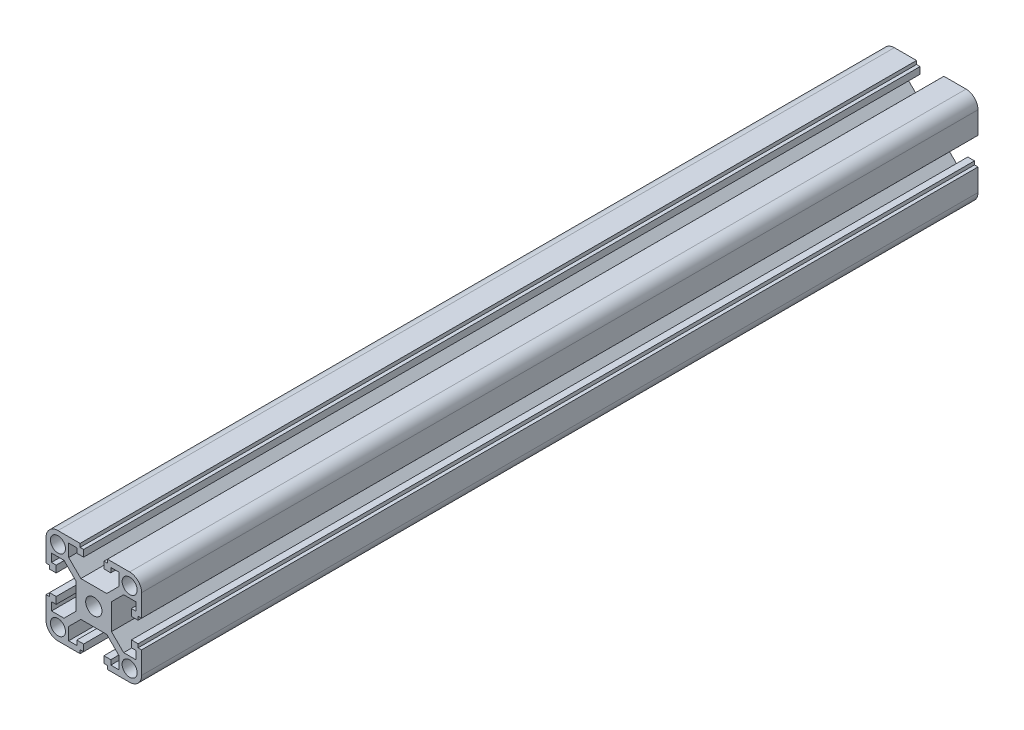
SolidWorks part; units mm, degrees
material "АД1 ГОСТ 4784-97"
ref_plane "Спереди" through (0, 0, 0) normal (0, 0, 1) x (1, 0, 0)
ref_plane "Сверху" through (0, 0, 0) normal (0, 1, 0) x (1, 0, 0)
ref_plane "Справа" through (0, 0, 0) normal (1, 0, 0) x (0, 0, -1)
ref_axis "ОсьX" through (-88.99, 0, 0) along (1, 0, 0)
ref_axis "ОсьZ" through (0, 55, 0) along (0, -1, 0)
ref_axis "ОсьY" through (0, 0, -88.99) along (0, 0, 1)
sketch "Эскиз1" plane through (0, 0, 0) normal (0, 0, 1) x (1, 0, 0)
  line L0 (-15, 20) -> (-5.7274, 20)
  line L1 (-5.7274, 20) -> (-5.7274, 18.5304)
  line L2 (-5.7274, 18.5304) -> (-4.25, 18.5304)
  line L3 (-4.25, 18.5304) -> (-4.25, 15.732)
  line L4 (-4.25, 15.732) -> (-7.1118, 15.732)
  line L5 (-7.1118, 15.732) -> (-7.1118, 17.7)
  line L6 (-7.1118, 17.7) -> (-10.5, 17.7)
  line L7 (-10.5, 17.7) -> (-10.5, 12.4799)
  line L8 (-10.5, 12.4799) -> (-5.4201, 7.4)
  line L9 (-20, 15) -> (-20, 5.7274)
  line L10 (0, 0) -> (0, 8.4096) construction
  line L11 (-15, 15) -> (0, 0) construction
  line L12 (10.5, 12.4799) -> (5.4201, 7.4)
  line L13 (10.5, 17.7) -> (10.5, 12.4799)
  line L14 (7.1118, 17.7) -> (10.5, 17.7)
  line L15 (7.1118, 15.732) -> (7.1118, 17.7)
  line L16 (4.25, 15.732) -> (7.1118, 15.732)
  line L17 (4.25, 18.5304) -> (4.25, 15.732)
  line L18 (5.7274, 18.5304) -> (4.25, 18.5304)
  line L19 (5.7274, 20) -> (5.7274, 18.5304)
  line L20 (15, 20) -> (5.7274, 20)
  line L21 (-5.4201, 7.4) -> (5.4201, 7.4)
  line L22 (-8.8445, 0) -> (0, 0) construction
  line L23 (-12.4799, 10.5) -> (-7.4, 5.4201)
  line L24 (-17.7, 10.5) -> (-12.4799, 10.5)
  line L25 (-17.7, 7.1118) -> (-17.7, 10.5)
  line L26 (-15.732, 7.1118) -> (-17.7, 7.1118)
  line L27 (-15.732, 4.25) -> (-15.732, 7.1118)
  line L28 (-18.5304, 4.25) -> (-15.732, 4.25)
  line L29 (-18.5304, 5.7274) -> (-18.5304, 4.25)
  line L30 (-20, 5.7274) -> (-18.5304, 5.7274)
  line L31 (18.5304, 5.7274) -> (18.5304, 4.25)
  line L32 (18.5304, 4.25) -> (15.732, 4.25)
  line L33 (15.732, 4.25) -> (15.732, 7.1118)
  line L34 (15.732, 7.1118) -> (17.7, 7.1118)
  line L35 (12.4799, 10.5) -> (7.4, 5.4201)
  line L36 (17.7, 10.5) -> (12.4799, 10.5)
  line L37 (17.7, 7.1118) -> (17.7, 10.5)
  line L38 (20, 5.7274) -> (18.5304, 5.7274)
  line L39 (20, 15) -> (20, 5.7274)
  line L40 (20, -15) -> (20, -5.7274)
  line L41 (20, -5.7274) -> (18.5304, -5.7274)
  line L42 (17.7, -7.1118) -> (17.7, -10.5)
  line L43 (17.7, -10.5) -> (12.4799, -10.5)
  line L44 (12.4799, -10.5) -> (7.4, -5.4201)
  line L45 (15.732, -7.1118) -> (17.7, -7.1118)
  line L46 (15.732, -4.25) -> (15.732, -7.1118)
  line L47 (18.5304, -4.25) -> (15.732, -4.25)
  line L48 (18.5304, -5.7274) -> (18.5304, -4.25)
  line L49 (-20, -5.7274) -> (-18.5304, -5.7274)
  line L50 (-18.5304, -5.7274) -> (-18.5304, -4.25)
  line L51 (-18.5304, -4.25) -> (-15.732, -4.25)
  line L52 (-15.732, -4.25) -> (-15.732, -7.1118)
  line L53 (-15.732, -7.1118) -> (-17.7, -7.1118)
  line L54 (-17.7, -7.1118) -> (-17.7, -10.5)
  line L55 (-17.7, -10.5) -> (-12.4799, -10.5)
  line L56 (-12.4799, -10.5) -> (-7.4, -5.4201)
  line L57 (-5.4201, -7.4) -> (5.4201, -7.4)
  line L58 (15, -20) -> (5.7274, -20)
  line L59 (5.7274, -20) -> (5.7274, -18.5304)
  line L60 (5.7274, -18.5304) -> (4.25, -18.5304)
  line L61 (4.25, -18.5304) -> (4.25, -15.732)
  line L62 (4.25, -15.732) -> (7.1118, -15.732)
  line L63 (7.1118, -15.732) -> (7.1118, -17.7)
  line L64 (7.1118, -17.7) -> (10.5, -17.7)
  line L65 (10.5, -17.7) -> (10.5, -12.4799)
  line L66 (10.5, -12.4799) -> (5.4201, -7.4)
  line L67 (-20, -15) -> (-20, -5.7274)
  line L68 (-10.5, -12.4799) -> (-5.4201, -7.4)
  line L69 (-10.5, -17.7) -> (-10.5, -12.4799)
  line L70 (-7.1118, -17.7) -> (-10.5, -17.7)
  line L71 (-7.1118, -15.732) -> (-7.1118, -17.7)
  line L72 (-4.25, -15.732) -> (-7.1118, -15.732)
  line L73 (-4.25, -18.5304) -> (-4.25, -15.732)
  line L74 (-5.7274, -18.5304) -> (-4.25, -18.5304)
  line L75 (-5.7274, -20) -> (-5.7274, -18.5304)
  line L76 (-15, -20) -> (-5.7274, -20)
  line L77 (-7.4, 5.4201) -> (-7.4, -5.4201)
  line L78 (7.4, 5.4201) -> (7.4, -5.4201)
  circle A0 centre (0, 0) radius 3.4
  circle A1 centre (-15, 15) radius 3.15
  arc A2 (-15, 20) -> (-20, 15) centre (-15, 15) ccw
  arc A3 (15, 20) -> (20, 15) centre (15, 15) cw
  circle A4 centre (15, 15) radius 3.15
  circle A5 centre (15, -15) radius 3.15
  arc A6 (15, -20) -> (20, -15) centre (15, -15) ccw
  arc A7 (-15, -20) -> (-20, -15) centre (-15, -15) cw
  circle A8 centre (-15, -15) radius 3.15
  dimension "D1" = 6.8
  dimension "D2" = 6.3
  dimension "D3" = 40
  dimension "D8" = 30
  dimension "D4" = 2.3
  dimension "D5" = 1.35
  dimension "D6" = 21
  dimension "D7" = 8.5
  dimension "D9" = 45
  dimension "D10" = 2.8
  dimension "D11" = 4
  dimension "D13" = 40
extrude "Бобышка-Вытянуть1" add sketch "Эскиз1" along normal mid plane 350
